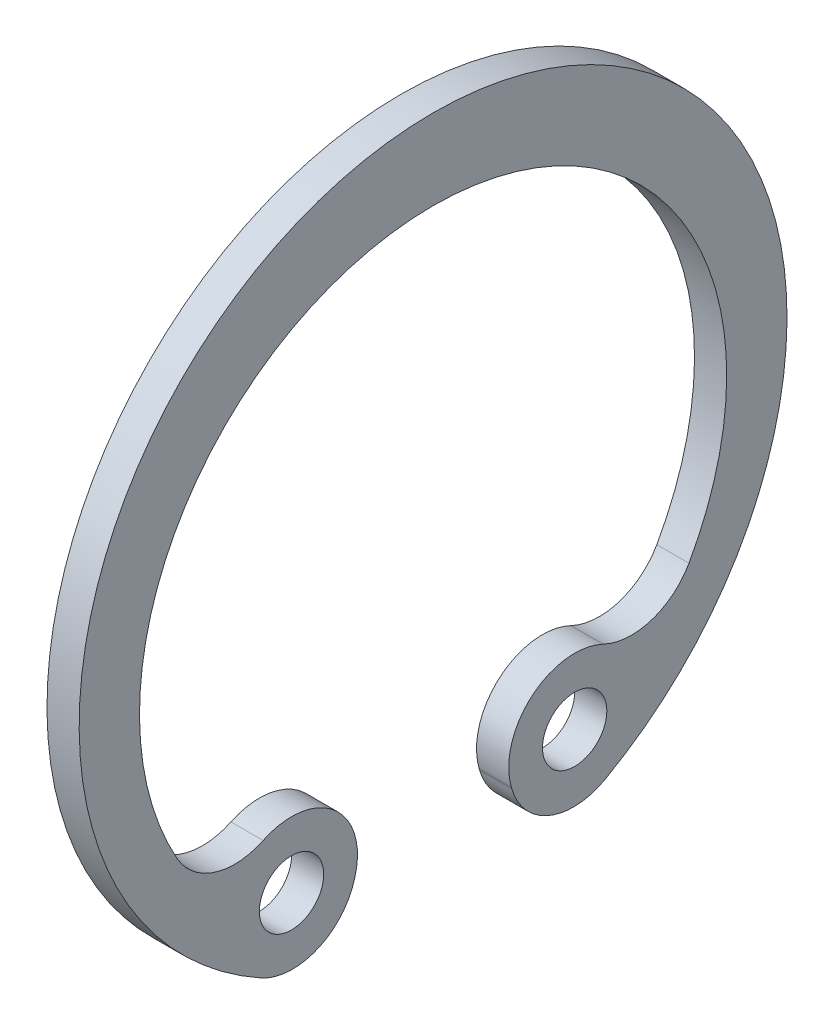
SolidWorks part; units mm, degrees
material "POM Acetal Copolymer"
ref_plane "Front Plane" through (0, 0, 0) normal (0, 0, 1) x (1, 0, 0)
ref_plane "Top Plane" through (0, 0, 0) normal (0, 1, 0) x (1, 0, 0)
ref_plane "Right Plane" through (0, 0, 0) normal (1, 0, 0) x (0, 0, -1)
ref_plane "Plane1" through (0, 0, 0) normal (1, 0, 0) x (0, 0, -1)
sketch "Sketch1" plane through (0, 0, 0) normal (1, 0, 0) x (0, 0, -1)
  line L0 (-2.449, -8.4263) -> (-2.4315, -8.3659)
  line L1 (2.4315, -8.3659) -> (2.449, -8.4263)
  arc A0 (5.3406, -9.6166) -> (-5.3406, -9.6166) centre (0, 0) ccw
  arc A1 (-5.3406, -9.6166) -> (-2.449, -8.4263) centre (-4.3695, -7.8681) ccw
  arc A2 (-2.4315, -8.3659) -> (-5.2832, -5.9437) centre (-4.4, -7.7937) ccw
  arc A3 (-5.2832, -5.9437) -> (-7.953, -5.0988) centre (-6.1663, -4.0937) cw
  arc A4 (-7.953, -5.0988) -> (7.953, -5.0988) centre (0, -0.625) cw
  arc A5 (7.953, -5.0988) -> (5.2832, -5.9437) centre (6.1663, -4.0937) cw
  arc A6 (5.2832, -5.9437) -> (2.4315, -8.3659) centre (4.4, -7.7937) ccw
  arc A7 (2.449, -8.4263) -> (5.3406, -9.6166) centre (4.3695, -7.8681) ccw
  circle A8 centre (4.4, -7.7937) radius 1
  circle A9 centre (-4.4, -7.7937) radius 1
extrude "Boss-Extrude1" add sketch "Sketch1" against normal blind 0.5 and the other way blind 0.5
